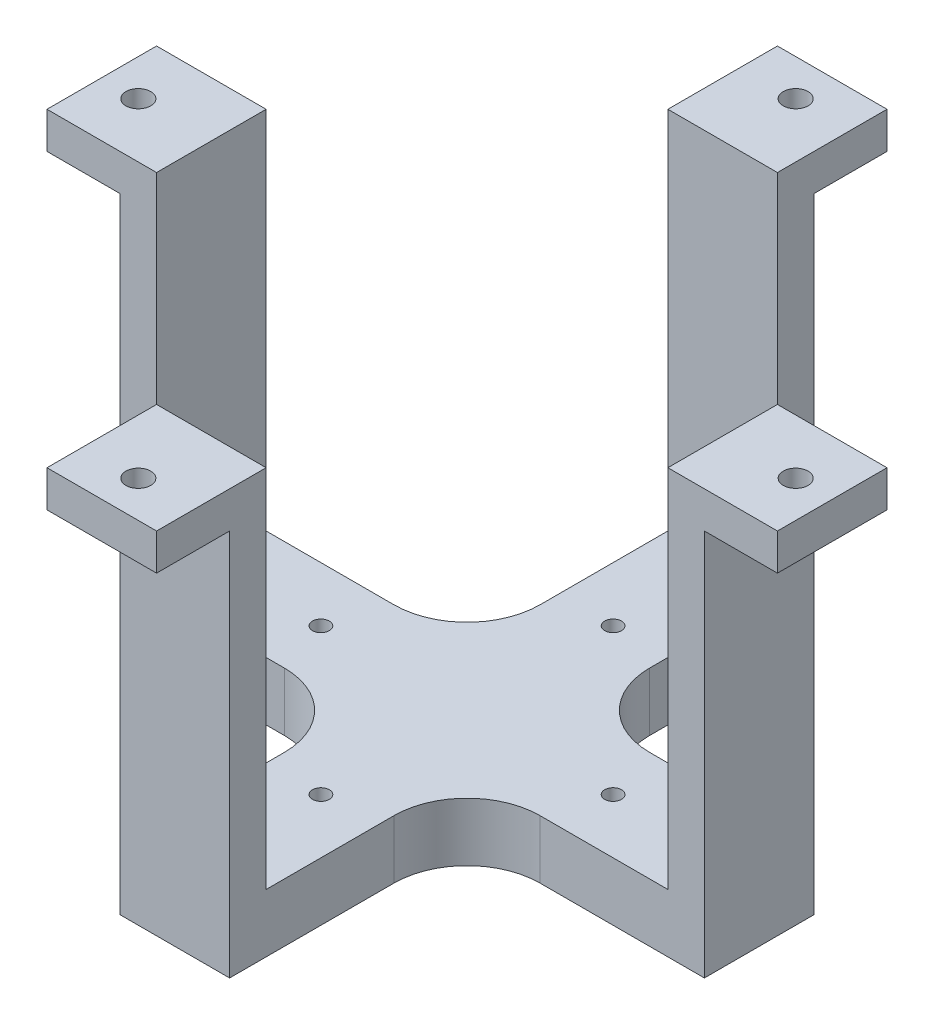
SolidWorks part; units mm, degrees
note: '?' marks a value the reader was unsure of.
ref_plane "Front Plane" through (0, 0, 0) normal (0, 0, 1) x (1, 0, 0)
ref_plane "Top Plane" through (0, 0, 0) normal (0, 1, 0) x (1, 0, 0)
ref_plane "Right Plane" through (0, 0, 0) normal (1, 0, 0) x (0, 0, -1)
sketch "Sketch2" plane through (0, 0, 0) normal (0, 1, 0) x (1, 0, 0)
  line L1 (-7.5, 40) -> (7.5, 40)
  line L2 (-7.5, 40) -> (-7.5, 0)
  line L3 (-7.5, 0) -> (7.5, 0)
  line L4 (7.5, 40) -> (7.5, 0)
  point P4 (0, 0)
  dimension "D1" = 15
  dimension "D2" = 40
extrude "Boss-Extrude1" add sketch "Sketch2" against normal blind 8
sketch "Sketch3" plane through (0, 0, 0) normal (0, 1, 0) x (1, 0, 0)
  line L0 (7.5, 0) -> (7.5, 40) construction
  line L1 (-7.5, 40) -> (7.5, 40)
  line L2 (-7.5, 40) -> (-7.5, 35)
  line L3 (-7.5, 35) -> (7.5, 35)
  line L4 (7.5, 40) -> (7.5, 35)
  dimension "D1" = 5
extrude "Boss-Extrude4" add sketch "Sketch3" along normal blind 50
sketch "Sketch6" plane through (0, 50, 0) normal (0, 1, 0) x (1, 0, 0)
  line L1 (-7.5, 40) -> (7.5, 40)
  line L2 (-7.5, 40) -> (-7.5, 50)
  line L3 (-7.5, 50) -> (7.5, 50)
  line L4 (7.5, 40) -> (7.5, 50)
  point P4 (0, 0)
  dimension "D1" = 10
extrude "Boss-Extrude5" add sketch "Sketch6" against normal blind 5
sketch "Sketch8" plane through (0, 45, 0) normal (0, -1, 0) x (1, 0, 0)
  line L0 (7.5, -50) -> (-7.5, -50) construction
  line L1 (7.5, -40) -> (7.5, -50) construction
  circle A0 centre (0, -45) radius 1.7
  point P2 (0, 0)
  point P5 (0, -50)
  point P6 (0, 0)
  point P9 (7.5, -45)
  dimension "D1" = 3.4
extrude "Cut-Extrude1" cut sketch "Sketch8" against normal through all
ref_axis "Axis1" through (0, -8.4, 0) along (0, 1, 0)?
pattern_circular "CirPattern1" count 4 over 360 about axis through (0, 0, 0) along (0, 1, 0) of "Boss-Extrude1", "Boss-Extrude4", "Boss-Extrude5", "Cut-Extrude1"
fillet "Fillet1" radius 10 4 edges at (-7.5, -4, -7.5) (7.5, -4, -7.5) (-7.5, -4, 7.5) (7.5, -4, 7.5)
sketch "Sketch9" plane through (0, -8, 0) normal (0, -1, 0) x (1, 0, 0)
  line L0 (0, 0) -> (0, 20) construction
  line L1 (0, 0) -> (20, 0) construction
  line L2 (0, 0) -> (0, -20) construction
  line L3 (0, 0) -> (-20, 0) construction
  circle A0 centre (0, 20) radius 1.15
  circle A1 centre (20, 0) radius 1.15
  circle A2 centre (0, -20) radius 1.15
  circle A3 centre (-20, 0) radius 1.15
  point P1 (0, 20)
  point P3 (20, 0)
  point P5 (0, -20)
  point P6 (-20, 0)
  dimension "D2" = 2.3
  dimension "D1" = 20
extrude "Cut-Extrude2" cut sketch "Sketch9" against normal through all
